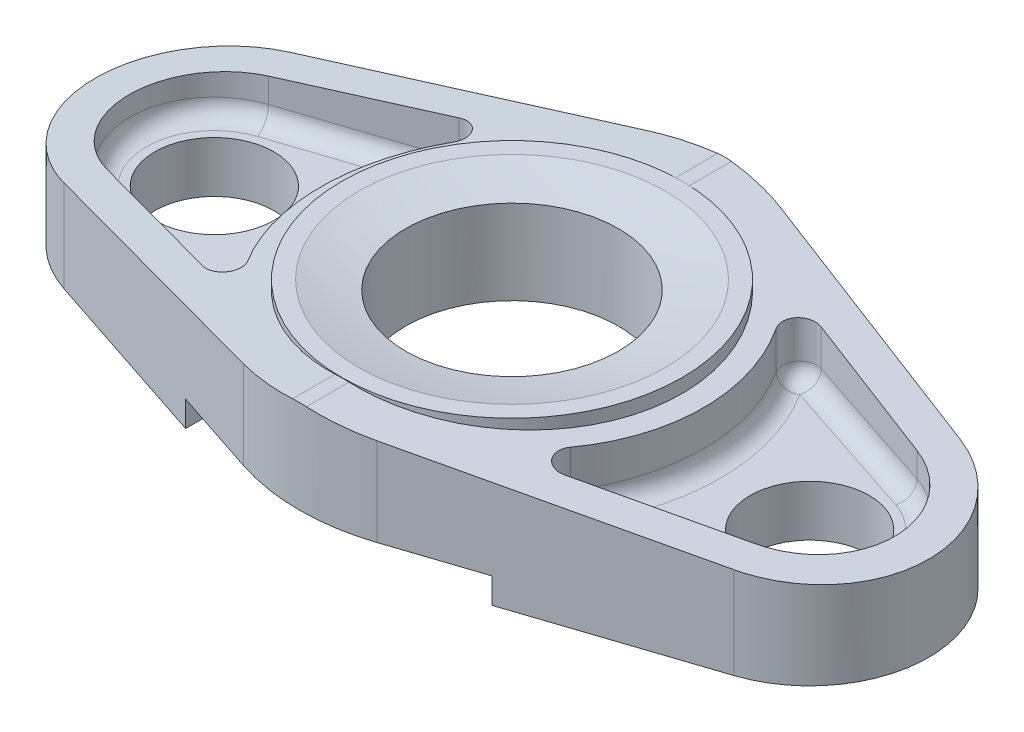
SolidWorks part; units mm, degrees
ref_plane "前视基准面" through (0, 0, 0) normal (0, 0, 1) x (1, 0, 0)
ref_plane "上视基准面" through (0, 0, 0) normal (0, 1, 0) x (1, 0, 0)
ref_plane "右视基准面" through (0, 0, 0) normal (1, 0, 0) x (0, 0, -1)
sketch "草图2" plane through (0, 0, 0) normal (0, 1, 0) x (1, 0, 0)
  line L0 (7.8571, 23.7332) -> (39.4, 13.2906)
  line L1 (0, 0) -> (0, 37.1111) construction
  line L2 (-7.8571, 23.7332) -> (-39.4, 13.2906)
  line L3 (0, 0) -> (19.0923, 0) construction
  line L4 (-7.8571, -23.7332) -> (-39.4, -13.2906)
  line L5 (7.8571, -23.7332) -> (39.4, -13.2906)
  arc A0 (-7.8571, -23.7332) -> (7.8571, -23.7332) centre (0, 0) ccw
  arc A1 (39.4, -13.2906) -> (39.4, 13.2906) centre (35, 0) ccw
  arc A2 (-39.4, -13.2906) -> (-39.4, 13.2906) centre (-35, 0) cw
  arc A3 (7.8571, 23.7332) -> (-7.8571, 23.7332) centre (0, 0) ccw
  dimension "D1" = 50
  dimension "D2" = 28
  dimension "D3" = 70
extrude "凸台-拉伸1" add sketch "草图2" along normal blind 14
sketch "草图3" plane through (0, 0, 0) normal (0, 0, 1) x (1, 0, 0)
  line L0 (-49, 10) -> (0, 14)
  line L1 (-49, 14) -> (-49, 0) construction
  line L2 (7.8571, 14) -> (-7.8571, 14) construction
  line L3 (-7.8571, 0) -> (7.8571, 0) construction
  dimension "D1" = 10
extrude "切除-拉伸1" cut sketch "草图3" against normal through all and the other way through all
mirror "镜向1" about plane through (0, 0, 0) normal (1, 0, 0) of "切除-拉伸1"
sketch "草图4" plane through (0, 0, 0) normal (0, -1, 0) x (1, 0, 0)
  line L0 (0, 0) -> (0, 16.2468) construction
  arc A0 (-39.4, 13.2906) -> (-39.4, -13.2906) centre (-35, 0) ccw construction
  arc A1 (-39.4, 13.2906) -> (-39.4, -13.2906) centre (-35, 0) ccw construction
  circle A2 centre (-35, 0) radius 7
  circle A3 centre (35, 0) radius 7
  dimension "D1" = 14
extrude "切除-拉伸2" cut sketch "草图4" against normal through all
sketch "草图5" plane through (0, 0, 0) normal (0, 1, 0) x (1, 0, 0)
  line L4 (-38.1429, -9.4933) -> (-6.6, -19.9359)
  line L5 (-6.6, 19.9359) -> (-38.1429, 9.4933)
  line L6 (-38.1429, -9.4933) -> (-14.2684, -17.3972)
  line L7 (-14.2684, 17.3972) -> (-38.1429, 9.4933)
  arc A1 (-14.2684, -17.3972) -> (-14.2684, 17.3972) centre (0, 0) cw
  arc A2 (-38.1429, 9.4933) -> (-38.1429, -9.4933) centre (-35, 0) ccw
  arc A3 (-38.1429, 9.4933) -> (-38.1429, -9.4933) centre (-35, 0) ccw
  dimension "D2" = 22.5
  dimension "D1" = 4
extrude "切除-拉伸3" cut sketch "草图5" along normal through all from offset 6
mirror "镜向2" about plane through (0, 0, 0) normal (1, 0, 0) of "切除-拉伸3"
sketch "草图7" plane through (0, 0, 0) normal (0, 1, 0) x (1, 0, 0)
  circle A0 centre (0, 0) radius 20
  dimension "D1" = 40
extrude "凸台-拉伸2" add sketch "草图7" along normal blind 14
sketch "草图6" plane through (0, 0, 0) normal (0, 0, 1) x (1, 0, 0)
  line L0 (-39.4, 0) -> (-7.8571, 0) construction
  line L1 (-18, 0) -> (18, 0)
  line L2 (-18, 0) -> (-18, 3)
  line L3 (-18, 3) -> (18, 3)
  line L4 (18, 0) -> (18, 3)
  point P6 (0, 0)
  dimension "D1" = 3
  dimension "D2" = 36
extrude "切除-拉伸4" cut sketch "草图6" against normal through all both and the other way through all
sketch "草图8" plane through (0, 0, 0) normal (0, 0, 1) x (1, 0, 0)
  line L0 (20, 14) -> (0, 14) construction
  line L1 (0, 14) -> (-20, 14) construction
  line L2 (20, 12.3673) -> (20, 14) construction
  line L3 (0, -0.2988) -> (0, 26.3137) construction
  line L4 (18, 14) -> (-18, 14)
  line L5 (0, 91.9487) -> (0, 11.9487)
  line L6 (0, 91.9487) -> (18, 14)
  arc A0 (18, 14) -> (-18, 14) centre (0, 91.9487) cw
  dimension "D1" = 2
  dimension "D2" = 80
revolve "切除-旋转3" cut sketch "草图8" angle 360 about L3 region at (6.7617, 13.1786, 0)
sketch "草图9" plane through (0, 3, 0) normal (0, -1, 0) x (1, 0, 0)
  circle A0 centre (0, 0) radius 12.5
  dimension "D1" = 25
extrude "切除-拉伸5" cut sketch "草图9" against normal through all both and the other way through all
fillet "圆角1" radius 10 2 edges at (0, 14, 22.5) (0, 14, -22.5)
fillet "圆角4" radius 2 12 edges at (26.2056, 6, 13.4452) (45, 6, 0) (-26.2056, 6, 13.4452) (-45, 6, 0) (-14.2684, 9.4176, 17.3972) (14.2684, 9.4176, 17.3972) (26.2056, 6, -13.4452) (14.2684, 9.4176, -17.3972) (22.5, 6, 0) (-14.2684, 9.4176, -17.3972) (-22.5, 6, 0) (-26.2056, 6, -13.4452)
